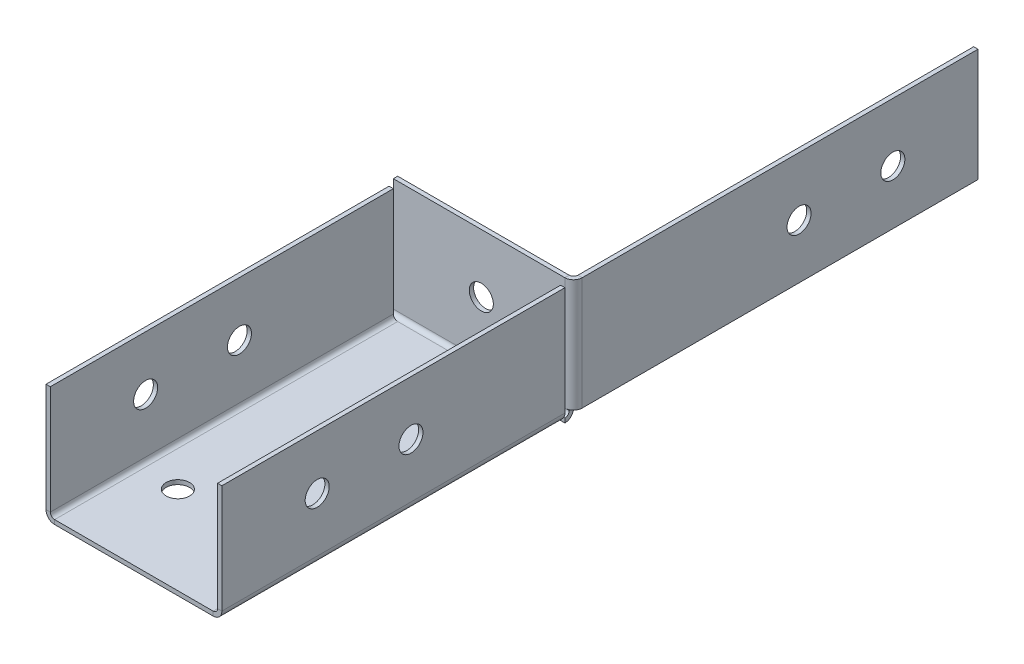
SolidWorks part; units mm, degrees
note: The reader was unsure of these and kept them because the rebuilt part matched: flange length of "Edge-Flange1", "Edge-Flange2", "Edge-Flange3", "Edge-Flange4".
ref_plane "Front Plane" through (0, 0, 0) normal (0, 0, 1) x (1, 0, 0)
ref_plane "Top Plane" through (0, 0, 0) normal (0, 1, 0) x (1, 0, 0)
ref_plane "Right Plane" through (0, 0, 0) normal (1, 0, 0) x (0, 0, -1)
sketch "Sketch1" plane through (0, 0, 0) normal (0, 1, 0) x (1, 0, 0)
  line L1 (-15, -30) -> (15, -30)
  line L2 (-15, -30) -> (-15, 30)
  line L3 (-15, 30) -> (15, 30)
  line L4 (15, -30) -> (15, 30)
  line L5 (-15, -30) -> (15, 30) construction
  line L6 (-15, 30) -> (15, -30) construction
  circle A0 centre (7.5, -15) radius 2
  circle A1 centre (0, 15) radius 2
  circle A2 centre (-7.5, -15) radius 2
  point P0 (0, 0)
  dimension "D3" = 4
  dimension "D4" = 4
  dimension "D5" = 4
  dimension "D7" = 7.5
  dimension "D1" = 60
  dimension "D2" = 30
  dimension "D6" = 15
  dimension "D8" = 15
  dimension "D9" = 15
  dimension "D10" = 7.5
  dimension "D11" = 15
base flange "Base-Flange1" sketch "Sketch1" thickness 0.7366 reverse thickness direction no parameters "D1"=0.7366
edge flange "Edge-Flange1" sketch "Sketch8" flange angle 90 flange length 20.7366 flange position material inside bend radius 0.7366 thickness 0.7366 relief rectangular parameters "D6"=10
sketch "Sketch8" plane through (0, 0, -30) normal (0, 0, -1) x (-1, 0, 0)
  line L0 (-15, 0) -> (15, 0) construction
  line L1 (-15, 0) -> (15, 0)
  line L2 (-15, 0) -> (-15, 20)
  line L3 (15, 20) -> (-15, 20)
  line L4 (15, 20) -> (15, 0)
  circle A1 centre (0, 10) radius 2.05
  dimension "D2" = 4.1
  dimension "D1" = 20
  dimension "D3" = 10
bend "EdgeBend1" bend radius 0.7366 bend angle 90 parameters "D5"=1
edge flange "Edge-Flange2" sketch "Sketch11" flange angle 90 flange length 20 flange position material inside bend radius 0.7366 thickness 0.7366 relief none parameters "D6"=10
sketch "Sketch11" plane through (15, 0, 0) normal (1, 0, 0) x (0, 0, -1)
  line L0 (-30, 0) -> (28.5268, 0) construction
  line L1 (-30, 0) -> (28.5268, 0)
  line L2 (-30, 0) -> (-30, 19.2634)
  line L3 (-30, 19.2634) -> (28.5268, 19.2634)
  line L4 (28.5268, 19.2634) -> (28.5268, 0)
bend "EdgeBend2" bend radius 0.7366 bend angle 90 parameters "D5"=2
edge flange "Edge-Flange3" sketch "Sketch14" flange angle 90 flange length 20 flange position material inside bend radius 0.7366 thickness 0.7366 relief none parameters "D6"=10
sketch "Sketch14" plane through (-15, 0, 0) normal (-1, 0, 0) x (0, 0, 1)
  line L0 (-28.5268, 0) -> (30, 0) construction
  line L1 (-28.5268, 0) -> (30, 0)
  line L2 (-28.5268, 0) -> (-28.5268, 19.2634)
  line L3 (-28.5268, 19.2634) -> (30, 19.2634)
  line L4 (30, 19.2634) -> (30, 0)
bend "EdgeBend3" bend radius 0.7366 bend angle 90 parameters "D5"=3
edge flange "Edge-Flange4" sketch "Sketch17" flange angle 90 flange length 69 flange position material outside bend radius 0.7366 thickness 0.7366 relief none parameters "D6"=10
sketch "Sketch17" plane through (15, 0, -30) normal (1, 0, 0) x (0, -1, 0)
  line L0 (-20, 0) -> (-0.7366, 0) construction
  line L1 (-20, 0) -> (-0.7366, 0)
  line L2 (-20, 0) -> (-20, 68.2634)
  line L3 (-20, 68.2634) -> (-0.7366, 68.2634)
  line L4 (-0.7366, 68.2634) -> (-0.7366, 0)
bend "EdgeBend4" bend radius 0.7366 bend angle 90 parameters "D5"=4
extrude "Cut-Extrude1" cut sketch "Sketch18" against normal through all normal cut yes
sketch "Sketch18" plane through (-385, -11.7404, -25.1261) normal (-1, 0, 0) x (0, 0, 1)
  circle A3 centre (-42.6105, 21.7404) radius 2.05
  circle A6 centre (-58.6105, 21.7404) radius 2.05
  circle A9 centre (22.8627, 21.7404) radius 2.05
  circle A12 centre (38.8627, 21.7404) radius 2.05
sketch "Bend-Lines1" [suppressed] plane through (0, 0, 0) normal (0, 1, 0) x (1, 0, 0)
sketch "Bounding-Box1" [suppressed] plane through (0, 0, 0) normal (0, 1, 0) x (1, 0, 0)
sketch "Sketch19" [suppressed] plane through (0, 0, 0) normal (0, 1, 0) x (1, 0, 0)
  line L0 (-5.7797, 29.1946) -> (-5.7797, 29.5946)
  line L7 (14.5946, -17.8198) -> (14.5946, -13.9247)
  line L8 (14.1946, -17.8198) -> (14.1946, -13.9247)
  line L9 (14.5946, -17.8198) -> (14.1946, -17.8198)
  line L10 (14.5946, -13.9247) -> (14.1946, -13.9247)
  line L11 (14.5946, -7.8198) -> (14.5946, -3.9247)
  line L12 (14.1946, -7.8198) -> (14.1946, -3.9247)
  line L13 (14.5946, -7.8198) -> (14.1946, -7.8198)
  line L14 (14.5946, -3.9247) -> (14.1946, -3.9247)
  line L15 (14.5946, 2.1802) -> (14.5946, 6.0753)
  line L16 (14.1946, 2.1802) -> (14.1946, 6.0753)
  line L17 (14.5946, 2.1802) -> (14.1946, 2.1802)
  line L18 (14.5946, 6.0753) -> (14.1946, 6.0753)
  line L19 (14.5946, 12.1802) -> (14.5946, 16.0753)
  line L20 (14.1946, 12.1802) -> (14.1946, 16.0753)
  line L21 (14.5946, 12.1802) -> (14.1946, 12.1802)
  line L22 (14.5946, 16.0753) -> (14.1946, 16.0753)
  line L23 (14.5946, 22.1802) -> (14.5946, 26.0753)
  line L24 (14.1946, 22.1802) -> (14.1946, 26.0753)
  line L25 (14.5946, 22.1802) -> (14.1946, 22.1802)
  line L26 (14.5946, 26.0753) -> (14.1946, 26.0753)
  line L29 (-14.1946, 27.6234) -> (-14.5946, 27.6234)
  line L30 (-14.5946, 28.5268) -> (-14.5946, -30)
  line L31 (-14.5946, 27.6234) -> (-14.5946, 25.2432)
  line L33 (-14.1946, 28.5268) -> (-14.1946, -30)
  line L35 (-7.8591, 29.1946) -> (-7.8591, 29.5946)
  line L36 (-13.8591, 29.1946) -> (-13.8591, 29.5946)
  line L37 (15, 29.5946) -> (-15, 29.5946)
  line L38 (-11.7797, 29.5946) -> (-13.8591, 29.5946)
  line L39 (15, 29.1946) -> (-15, 29.1946)
  line L40 (-11.7797, 29.1946) -> (-13.8591, 29.1946)
  line L41 (-11.7797, 29.1946) -> (-11.7797, 29.5946)
  line L42 (-5.7797, 29.1946) -> (-7.8591, 29.1946)
  line L43 (-5.7797, 29.5946) -> (-7.8591, 29.5946)
  line L44 (0.2203, 29.1946) -> (0.2203, 29.5946)
  line L45 (-1.8591, 29.1946) -> (-1.8591, 29.5946)
  line L46 (0.2203, 29.1946) -> (-1.8591, 29.1946)
  line L47 (0.2203, 29.5946) -> (-1.8591, 29.5946)
  line L48 (6.2203, 29.1946) -> (6.2203, 29.5946)
  line L49 (4.1409, 29.1946) -> (4.1409, 29.5946)
  line L50 (6.2203, 29.1946) -> (4.1409, 29.1946)
  line L51 (6.2203, 29.5946) -> (4.1409, 29.5946)
  line L52 (12.2203, 29.1946) -> (12.2203, 29.5946)
  line L53 (10.1409, 29.1946) -> (10.1409, 29.5946)
  line L54 (12.2203, 29.1946) -> (10.1409, 29.1946)
  line L55 (12.2203, 29.5946) -> (10.1409, 29.5946)
  line L56 (15.3312, 34.9645) -> (15.3312, 38.4932)
  line L57 (15.3312, 48.4932) -> (14.9312, 48.4932)
  line L58 (15.3312, 30.2624) -> (15.3312, 49.5258)
  line L59 (15.3312, 44.9645) -> (15.3312, 48.4932)
  line L60 (14.9312, 30.2624) -> (14.9312, 49.5258)
  line L61 (14.9312, 44.9645) -> (14.9312, 48.4932)
  line L62 (15.3312, 44.9645) -> (14.9312, 44.9645)
  line L63 (14.9312, 34.9645) -> (14.9312, 38.4932)
  line L64 (15.3312, 34.9645) -> (14.9312, 34.9645)
  line L65 (15.3312, 38.4932) -> (14.9312, 38.4932)
  line L66 (-14.1946, 27.6234) -> (-14.1946, 25.2432)
  line L67 (-14.1946, 25.2432) -> (-14.5946, 25.2432)
  line L68 (-14.1946, 15.2432) -> (-14.5946, 15.2432)
  line L69 (-14.1946, 17.6234) -> (-14.1946, 15.2432)
  line L71 (-14.1946, 17.6234) -> (-14.5946, 17.6234)
  line L72 (-14.5946, 17.6234) -> (-14.5946, 15.2432)
  line L73 (-14.1946, 5.2432) -> (-14.5946, 5.2432)
  line L74 (-14.1946, 7.6234) -> (-14.1946, 5.2432)
  line L75 (-14.1946, 7.6234) -> (-14.5946, 7.6234)
  line L76 (-14.5946, 7.6234) -> (-14.5946, 5.2432)
  line L77 (-14.1946, -4.7568) -> (-14.5946, -4.7568)
  line L78 (-14.1946, -2.3766) -> (-14.1946, -4.7568)
  line L79 (-14.1946, -2.3766) -> (-14.5946, -2.3766)
  line L80 (-14.5946, -2.3766) -> (-14.5946, -4.7568)
  line L81 (-14.1946, -14.7568) -> (-14.5946, -14.7568)
  line L82 (-14.1946, -12.3766) -> (-14.1946, -14.7568)
  line L83 (-14.1946, -12.3766) -> (-14.5946, -12.3766)
  line L84 (-14.5946, -12.3766) -> (-14.5946, -14.7568)
  line L85 (-14.1946, -24.7568) -> (-14.5946, -24.7568)
  line L86 (-14.1946, -22.3766) -> (-14.1946, -24.7568)
  line L87 (-14.1946, -22.3766) -> (-14.5946, -22.3766)
  line L88 (-14.5946, -22.3766) -> (-14.5946, -24.7568)
  dimension "D4" = 0.2
  dimension "D6" = 0.2
  dimension "D7" = 0.2
  dimension "D9" = 0.2
  dimension "D10" = 0.2
  dimension "D12" = 0.2
  dimension "D8" = 5
  dimension "D11" = 2
  dimension "D13" = 6
extrude "Cut-Extrude2" [suppressed] cut sketch "Sketch19" against normal blind 10
sheet metal parameters "Sheet-Metal1" thickness 0.7366 parameters "D1"=0.7366
flat pattern "Flat-Pattern1" [suppressed]
sketch "Bend-Lines2" plane through (0, 0, 0) normal (0, 1, 0) x (1, 0, 0)
sketch "Bounding-Box2" [suppressed] plane through (0, 0, 0) normal (0, 1, 0) x (1, 0, 0)
sheet metal parameters "Sheet-Metal2" thickness 0.7366 parameters "D1"=0.7366
flat pattern "Flat-Pattern1" [suppressed]
sketch "Bend-Lines2" plane through (0, 0, 0) normal (0, 1, 0) x (1, 0, 0)
sketch "Bounding-Box2" [suppressed] plane through (0, 0, 0) normal (0, 1, 0) x (1, 0, 0)
bend of the flat pattern "Flatten-<EdgeBend1>1"
sheet metal parameters "Sheet-Metal3" thickness 0.7366 parameters "D1"=0.7366
flat pattern "Flat-Pattern1" [suppressed]
sketch "Bend-Lines2" plane through (0, 0, 0) normal (0, 1, 0) x (1, 0, 0)
sketch "Bounding-Box2" [suppressed] plane through (0, 0, 0) normal (0, 1, 0) x (1, 0, 0)
bend of the flat pattern "Flatten-<EdgeBend1>1"
bend of the flat pattern "Flatten-<EdgeBend2>1"
sheet metal parameters "Sheet-Metal4" thickness 0.7366 parameters "D1"=0.7366
flat pattern "Flat-Pattern1" [suppressed]
sketch "Bend-Lines2" plane through (0, 0, 0) normal (0, 1, 0) x (1, 0, 0)
sketch "Bounding-Box2" [suppressed] plane through (0, 0, 0) normal (0, 1, 0) x (1, 0, 0)
bend of the flat pattern "Flatten-<EdgeBend1>1"
bend of the flat pattern "Flatten-<EdgeBend2>1"
bend of the flat pattern "Flatten-<EdgeBend3>1"
sheet metal parameters "Sheet-Metal5" thickness 0.7366 parameters "D1"=0.7366
flat pattern "Flat-Pattern1" [suppressed]
sketch "Bend-Lines2" plane through (0, 0, 0) normal (0, 1, 0) x (1, 0, 0)
sketch "Bounding-Box2" [suppressed] plane through (0, 0, 0) normal (0, 1, 0) x (1, 0, 0)
bend of the flat pattern "Flatten-<EdgeBend1>1"
bend of the flat pattern "Flatten-<EdgeBend2>1"
bend of the flat pattern "Flatten-<EdgeBend3>1"
bend of the flat pattern "Flatten-<EdgeBend4>1"
sheet metal parameters "Sheet-Metal7" thickness 0.7366 parameters "D1"=0.7366
flat pattern "Flat-Pattern1"
sketch "Bend-Lines2" plane through (0, 0, 0) normal (0, 1, 0) x (1, 0, 0)
  line L0 (15.1312, 30.2624) -> (15.1312, 49.5258) construction
  line L1 (-14.3946, 28.5268) -> (-14.3946, -30) construction
  line L2 (14.3946, -30) -> (14.3946, 28.5268) construction
  line L3 (15, 29.3946) -> (-15, 29.3946) construction
  line L4 (15.1312, 30.2624) -> (15.1312, 49.5258) construction
  line L5 (-14.3946, 28.5268) -> (-14.3946, -30) construction
  line L6 (14.3946, -30) -> (14.3946, 28.5268) construction
  line L7 (15, 29.3946) -> (-15, 29.3946) construction
sketch3d "Bounding-Box2" [suppressed]
  line L0 (83.5258, 49.5258, 0) -> (-33.7892, 49.5258, 0) construction
  line L1 (83.5258, -30, 0) -> (-33.7892, -30, 0) construction
  line L2 (83.5258, 49.5258, 0) -> (83.5258, -30, 0) construction
  line L3 (-33.7892, 49.5258, 0) -> (-33.7892, -30, 0) construction
bend of the flat pattern "Flatten-<EdgeBend1>1"
bend of the flat pattern "Flatten-<EdgeBend2>1"
bend of the flat pattern "Flatten-<EdgeBend3>1"
bend of the flat pattern "Flatten-<EdgeBend4>1"
